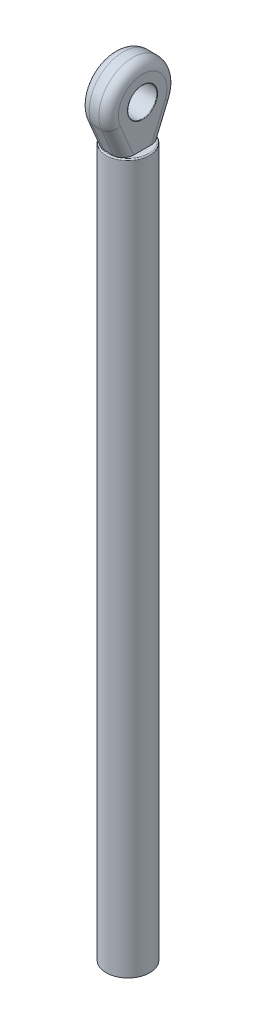
SolidWorks part; units mm, degrees
ref_plane "前视基准面" through (0, 0, 0) normal (0, 0, 1) x (1, 0, 0)
ref_plane "上视基准面" through (0, 0, 0) normal (0, 1, 0) x (1, 0, 0)
ref_plane "右视基准面" through (0, 0, 0) normal (1, 0, 0) x (0, 0, -1)
sketch "草图1" plane through (0, 0, 0) normal (0, 1, 0) x (1, 0, 0)
  circle A0 centre (0, 0) radius 45
  circle A1 centre (0, 0) radius 22.5
  dimension "D1" = 90
  dimension "D2" = 45
extrude "凸台-拉伸1" add sketch "草图1" along normal blind 1450
sketch "草图2" plane through (0, 1450, 0) normal (0, 1, 0) x (1, 0, 0)
  circle A0 centre (0, 0) radius 45
  circle A1 centre (0, 0) radius 45 construction
extrude "凸台-拉伸2" add sketch "草图2" along normal blind 10
sketch "草图3" plane through (0, 1460, 0) normal (0, 1, 0) x (1, 0, 0)
  line L0 (0, -1000) -> (0, 49000) construction
  line L1 (-1000, 0) -> (49000, 0) construction
  line L2 (-30, 75) -> (30, 75)
  line L3 (-30, 75) -> (-30, -75)
  line L4 (-30, -75) -> (30, -75)
  line L5 (30, 75) -> (30, -75)
  dimension "D1" = 60
  dimension "D2" = 150
extrude "凸台-拉伸3" add sketch "草图3" along normal blind 200
sketch "草图4" plane through (30, 0, 0) normal (1, 0, 0) x (0, 0, -1)
  line L0 (0, 1210) -> (0, 51210) construction
  line L1 (-75, 1660) -> (75, 1660) construction
  line L4 (-33.541, 1460) -> (33.541, 1460) construction
  line L5 (75, 1660) -> (75, 1460)
  line L6 (-75, 1660) -> (75, 1660)
  line L7 (75, 1460) -> (40, 1460)
  line L8 (40, 1460) -> (64.4495, 1517.6821)
  line L9 (-75, 1660) -> (-75, 1460)
  line L10 (-75, 1460) -> (-40, 1460)
  line L11 (-40, 1460) -> (-64.4495, 1517.6821)
  arc A0 (-64.4495, 1517.6821) -> (64.4495, 1517.6821) centre (0, 1545) cw
  circle A1 centre (0, 1545) radius 30
  point P5 (0, 1660)
  dimension "D1" = 70
  dimension "D3" = 60
  dimension "D2" = 85
  dimension "D4" = 40
extrude "切除-拉伸1" cut sketch "草图4" against normal through all
fillet "圆角1" radius 20 6 edges at (30, 1488.841, 52.2247) (30, 1488.841, -52.2247) (-30, 1488.841, 52.2247) (-30, 1488.841, -52.2247) (30, 1615, 0) (-30, 1615, 0)
fillet "圆角2" radius 2.5 1 edges at (0, 1460, 45)
fillet "圆角3" radius 1 1 edges at (30, 1545, -30)
